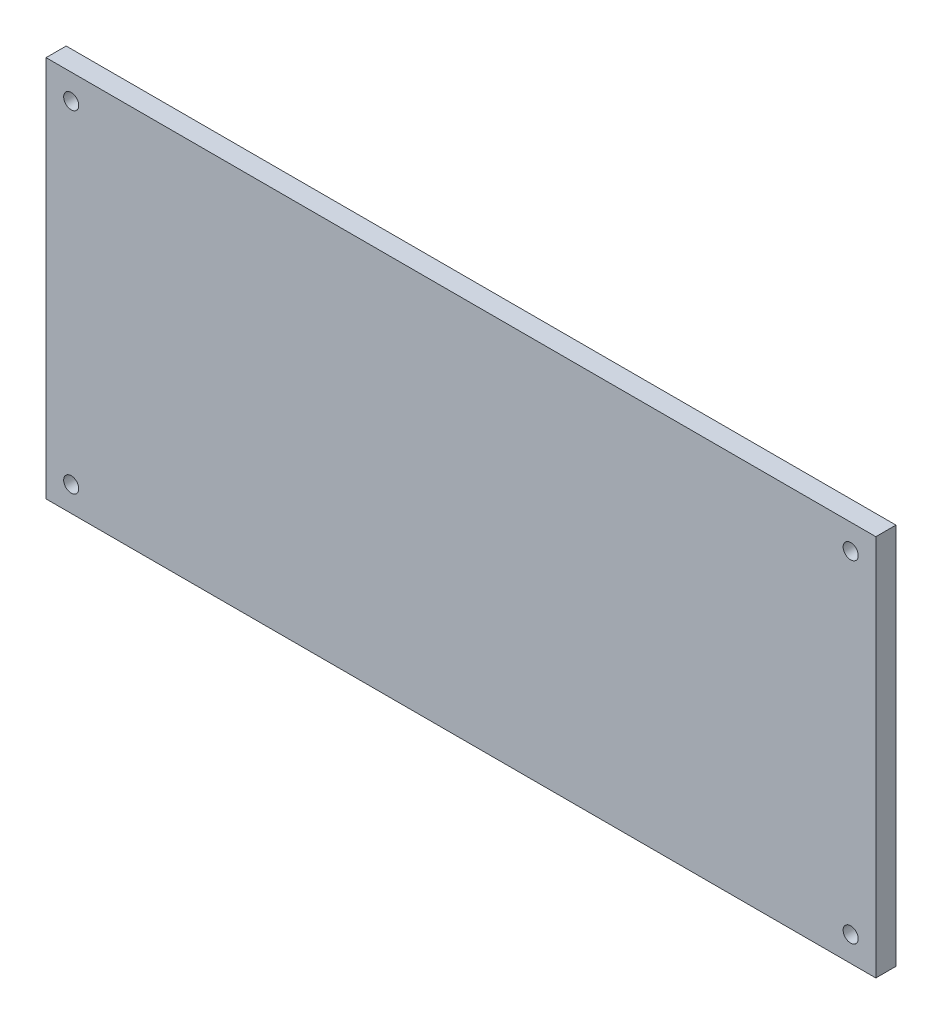
SolidWorks part; units mm, degrees
ref_plane "Front Plane" through (0, 0, 0) normal (0, 0, 1) x (1, 0, 0)
ref_plane "Top Plane" through (0, 0, 0) normal (0, 1, 0) x (1, 0, 0)
ref_plane "Right Plane" through (0, 0, 0) normal (1, 0, 0) x (0, 0, -1)
sketch "Sketch1" plane through (0, 0, 0) normal (0, 0, 1) x (1, 0, 0)
  line L0 (73.5512, 71.3362) -> (73.5512, -4.6638) construction
  line L1 (-8.9488, 71.3362) -> (156.0512, 71.3362)
  line L2 (-8.9488, 71.3362) -> (-8.9488, -4.6638)
  line L3 (-8.9488, -4.6638) -> (156.0512, -4.6638)
  line L4 (156.0512, 71.3362) -> (156.0512, -4.6638)
  line L5 (-8.9488, 33.3362) -> (156.0512, 33.3362) construction
  circle A0 centre (-3.9488, 0.3362) radius 1.5
  circle A1 centre (151.0512, 0.3362) radius 1.5
  circle A2 centre (151.0512, 66.3362) radius 1.5
  circle A3 centre (-3.9488, 66.3362) radius 1.5
  dimension "D1" = 3
  dimension "D5" = 5
  dimension "D2" = 76
  dimension "D3" = 165
  dimension "D4" = 5
extrude "Boss-Extrude1" add sketch "Sketch1" along normal blind 4
